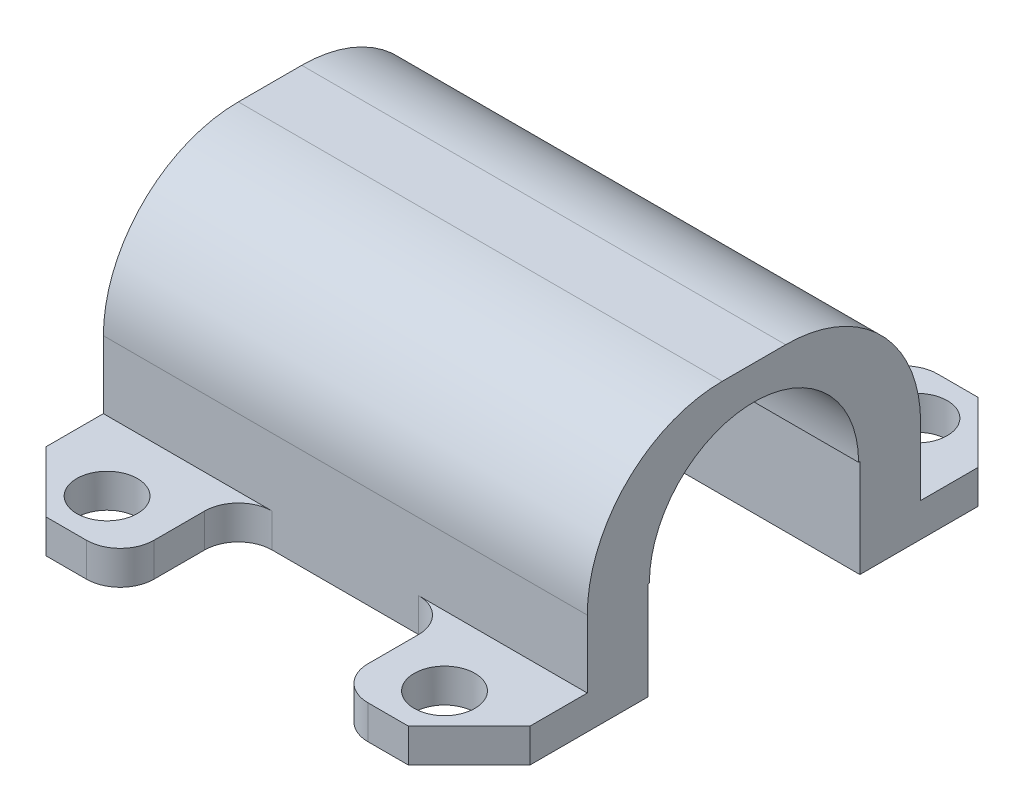
SolidWorks part; units mm, degrees
ref_plane "Front Plane" through (0, 0, 0) normal (0, 0, 1) x (1, 0, 0)
ref_plane "Top Plane" through (0, 0, 0) normal (0, 1, 0) x (1, 0, 0)
ref_plane "Right Plane" through (0, 0, 0) normal (1, 0, 0) x (0, 0, -1)
sketch "Sketch1" plane through (0, 0, 0) normal (0, 1, 0) x (1, 0, 0)
  line L0 (26.4739, -52.0178) -> (24.6739, -53.8178)
  line L1 (24.6739, -53.8178) -> (13.9339, -53.8178)
  line L2 (13.9339, -53.8178) -> (12.1339, -52.0178)
  line L3 (12.1339, -52.0178) -> (12.1339, -38.7393)
  line L4 (12.1339, -38.7393) -> (13.9339, -36.9393)
  line L5 (13.9339, -36.9393) -> (24.6739, -36.9393)
  line L6 (24.6739, -36.9393) -> (26.4739, -38.7393)
  line L7 (26.4739, -38.7393) -> (26.4739, -52.0178)
  dimension "D1" = 10.74
  dimension "D2" = 10.74
  dimension "D3" = 1.8
  dimension "D4" = 1.8
  dimension "D5" = 135
  dimension "D6" = 1.8
extrude "Boss-Extrude1" add sketch "Sketch1" along normal blind 2.5
sketch "Sketch2" plane through (0, 2.5, 0) normal (0, 1, 0) x (1, 0, 0)
  line L0 (12.1339, -38.7393) -> (12.1339, -52.0178) construction
  line L1 (26.4739, -52.0178) -> (26.4739, -38.7393) construction
  line L2 (13.9339, -53.8178) -> (24.6739, -53.8178) construction
  line L3 (24.6739, -36.9393) -> (13.9339, -36.9393) construction
  circle A0 centre (24.3039, -52.3778) radius 0.9
  circle A1 centre (14.3039, -52.3778) radius 0.9
  circle A2 centre (14.3039, -38.3793) radius 0.9
  circle A3 centre (24.3039, -38.3793) radius 0.9
  dimension "D1" = 1.8
  dimension "D2" = 1.8
  dimension "D3" = 1.8
  dimension "D4" = 1.8
  dimension "D5" = 2.17
  dimension "D6" = 2.17
  dimension "D7" = 2.17
  dimension "D8" = 2.17
  dimension "D9" = 1.44
  dimension "D10" = 1.44
  dimension "D11" = 1.44
  dimension "D12" = 1.44
extrude "Cut-Extrude1" cut sketch "Sketch2" against normal blind 2.5
sketch "Sketch3" plane through (0, 2.5, 0) normal (0, 1, 0) x (1, 0, 0)
  line L0 (26.4739, -52.0178) -> (26.4739, -38.7393) construction
  line L1 (26.4739, -50.3178) -> (12.1339, -50.3178)
  line L2 (26.4739, -50.3178) -> (26.4739, -40.4393)
  line L3 (26.4739, -40.4393) -> (12.1339, -40.4393)
  line L4 (12.1339, -50.3178) -> (12.1339, -40.4393)
  line L5 (12.1339, -38.7393) -> (12.1339, -52.0178) construction
  line L6 (13.9339, -53.8178) -> (24.6739, -53.8178) construction
  line L7 (24.6739, -36.9393) -> (13.9339, -36.9393) construction
  dimension "D1" = 3.5
  dimension "D2" = 3.5
extrude "Boss-Extrude2" add sketch "Sketch3" along normal blind 4.5
sketch "Sketch4" plane through (12.1339, 0, 0) normal (-1, 0, 0) x (0, 0, 1)
  line L0 (38.7393, 0) -> (52.0178, 0) construction
  line L1 (50.3178, 7) -> (50.3178, 2.5) construction
  circle A0 centre (45.3778, 2.9) radius 3.1
  dimension "D1" = 6.2
  dimension "D2" = 2.9
  dimension "D3" = 4.94
extrude "Cut-Extrude2" cut sketch "Sketch4" against normal through all
sketch "Sketch5" plane through (12.1339, 0, 0) normal (-1, 0, 0) x (0, 0, 1)
  line L7 (38.7393, 0) -> (44.2823, 0) construction
  line L8 (42.2393, 0) -> (48.5178, 0)
  line L9 (42.2393, 0) -> (42.2393, 2.9)
  line L10 (42.2393, 2.9) -> (48.5178, 2.9)
  line L11 (48.5178, 0) -> (48.5178, 2.9)
  line L12 (50.3178, 7) -> (50.3178, 2.5) construction
  line L13 (40.4393, 7) -> (40.4393, 2.5) construction
  dimension "D1" = 1.8
  dimension "D2" = 1.8
  dimension "D3" = 2.9
extrude "Cut-Extrude3" cut sketch "Sketch5" against normal through all
fillet "Fillet1" radius 4 2 edges at (19.3039, 7, 40.4393) (19.3039, 7, 50.3178)
sketch "Sketch7" plane through (0, 2.5, 0) normal (0, 1, 0) x (1, 0, 0)
  line L0 (13.9339, -53.8178) -> (24.6739, -53.8178) construction
  line L1 (22.4739, -53.8178) -> (16.1339, -53.8178)
  line L2 (22.4739, -53.8178) -> (22.4739, -50.3178)
  line L3 (22.4739, -50.3178) -> (16.1339, -50.3178)
  line L4 (16.1339, -53.8178) -> (16.1339, -50.3178)
  line L5 (26.4739, -50.3178) -> (12.1339, -50.3178) construction
  line L6 (24.6739, -36.9393) -> (13.9339, -36.9393) construction
  line L7 (22.4739, -36.9393) -> (16.1339, -36.9393)
  line L8 (22.4739, -36.9393) -> (22.4739, -40.4393)
  line L9 (22.4739, -40.4393) -> (16.1339, -40.4393)
  line L10 (16.1339, -36.9393) -> (16.1339, -40.4393)
  line L11 (12.1339, -40.4393) -> (26.4739, -40.4393) construction
  line L12 (26.4739, -40.4393) -> (26.4739, -38.7393) construction
  line L13 (12.1339, -38.7393) -> (12.1339, -40.4393) construction
  line L14 (26.4739, -52.0178) -> (26.4739, -50.3178) construction
  line L15 (12.1339, -50.3178) -> (12.1339, -52.0178) construction
  dimension "D1" = 4
  dimension "D2" = 4
  dimension "D3" = 4
  dimension "D4" = 4
extrude "Cut-Extrude5" cut sketch "Sketch7" against normal through all
fillet "Fillet2" radius 1 8 edges at (16.1339, 1.25, 50.3178) (16.1339, 1.25, 53.8178) (22.4739, 1.25, 50.3178) (22.4739, 1.25, 53.8178) (22.4739, 1.25, 40.4393) (16.1339, 1.25, 40.4393) (16.1339, 1.25, 36.9393) (22.4739, 1.25, 36.9393)
sketch "Sketch8" plane through (12.1339, 0, 0) normal (-1, 0, 0) x (0, 0, 1)
  line L0 (36.9393, 2.5) -> (36.9393, 0) construction
  line L1 (40.4393, 2.5) -> (36.9393, 2.5)
  line L2 (40.4393, 2.5) -> (40.4393, 1)
  line L3 (40.4393, 1) -> (36.9393, 1)
  line L4 (36.9393, 2.5) -> (36.9393, 1)
  line L5 (53.8178, 2.5) -> (53.8178, 0) construction
  line L6 (50.3178, 2.5) -> (53.8178, 2.5)
  line L7 (50.3178, 2.5) -> (50.3178, 1)
  line L8 (50.3178, 1) -> (53.8178, 1)
  line L9 (53.8178, 2.5) -> (53.8178, 1)
  dimension "D1" = 1.5
  dimension "D2" = 1.5
extrude "Cut-Extrude6" cut sketch "Sketch8" against normal through all
